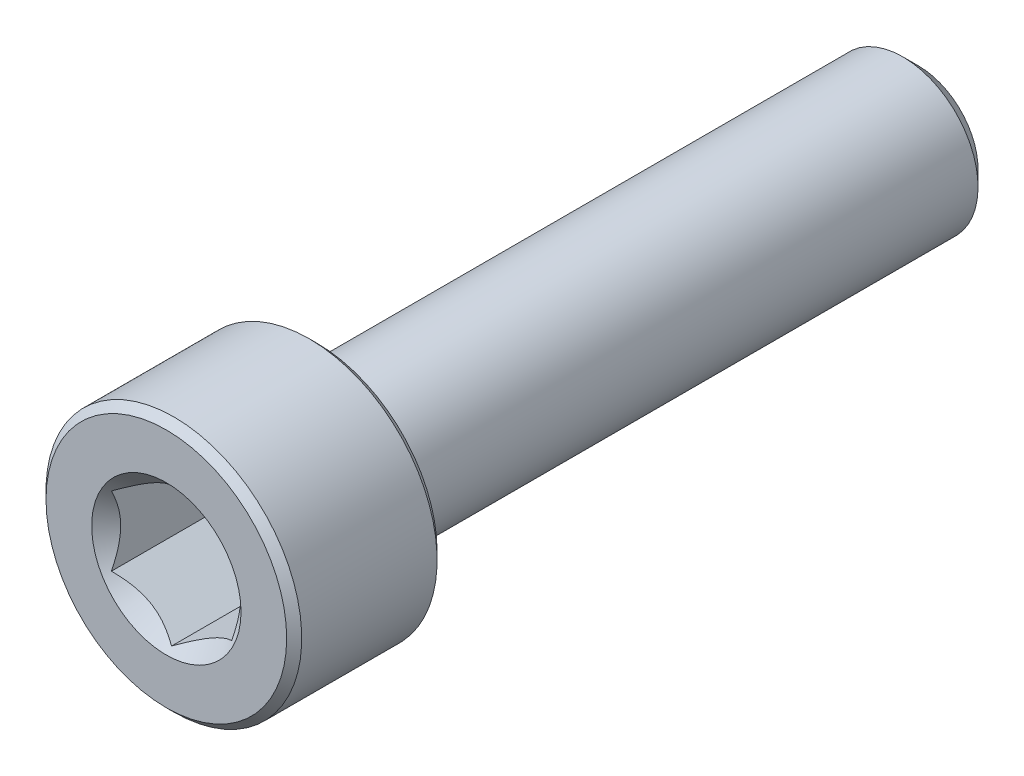
SolidWorks part; units mm, degrees
ref_plane "Front Plane" through (0, 0, 0) normal (0, 0, 1) x (1, 0, 0)
ref_plane "Top Plane" through (0, 0, 0) normal (0, 1, 0) x (1, 0, 0)
ref_plane "Right Plane" through (0, 0, 0) normal (1, 0, 0) x (0, 0, -1)
sketch "Sketch1" plane through (0, 0, 0) normal (1, 0, 0) x (0, 0, -1)
  line L0 (-12.5, 0) -> (12.5, 0) construction
  line L1 (12.5, 0) -> (12.5, 1.9804) construction
  line L2 (12.5, 1.9804) -> (11.9804, 2.5) construction
  line L3 (11.9804, 2.5) -> (11.9, 2.5) construction
  line L4 (11.9, 2.5) -> (-7.5, 2.5) construction
  line L5 (-7.5, 2.5) -> (-7.5, 4.25) construction
  line L6 (-7.5, 4.25) -> (-12.5, 4.25) construction
  line L7 (-12.5, 4.25) -> (-12.5, 0) construction
  line L8 (12.5, 1.9804) -> (12.5, 2.5) construction
  line L9 (12.45, 2.5866) -> (12.85, 1.8938) construction
  line L10 (12.85, 1.8938) -> (13.25, 2.5866) construction
  line L11 (13.25, 2.5866) -> (12.45, 2.5866) construction
  line L12 (12.85, 2.5866) -> (12.85, 2.5) construction
  line L13 (12.85, 1.8938) -> (12.85, 1.9804) construction
  line L14 (12.8, 1.9804) -> (12.9, 1.9804) construction
  line L15 (12.5, 2.5) -> (13.2, 2.5) construction
  line L16 (12.475, 2.5433) -> (13.225, 2.5433) construction
  line L17 (12.5, 0) -> (12.5, -2.5) construction
  line L18 (-7.75, 4.25) -> (-7.5, 4) construction
  line L19 (-12.25, 4.25) -> (-12.5, 4) construction
  line L20 (-7.5, 2.5) -> (-7.5, 0) construction
  line L21 (-7.5, 1.25) -> (-0.8333, 1.25) construction
  line L22 (-0.8333, 1.25) -> (5.8333, 1.25) construction
  line L23 (5.8333, 1.25) -> (12.5, 1.25) construction
  line L24 (-0.8333, 1.25) -> (-0.8333, 2.5) construction
  line L25 (-0.8333, 2.5) -> (-0.8333, 4.25) construction
  line L26 (5.8333, 1.25) -> (5.8333, 4.25) construction
  point P0 (-12.5, 2)
  point P3 (10.5, 2.5)
  point P4 (0, 0)
  point P18 (5.8333, 2.5)
  point P22 (12.85, 1.9804)
  point P24 (11.9, 2.5)
  point P25 (12.85, 2.5)
  point P28 (12.85, 2.5433)
  point P29 (10.5, -2.5)
  point P30 (-0.8333, 2.5)
  point P31 (-10, 4.25)
  point P37 (-8.375, 4.25)
  point P38 (-12.125, 4.25)
  point P45 (-0.8333, 1.25)
  point P46 (5.8333, 1.25)
  dimension "D2" = 0.1
  dimension "D7" = 0.25
  dimension "D8" = 0.25
  dimension "D9" = 0.25
  dimension "D10" = 0.125
  dimension "D11" = 0.625
  dimension "Drive Size" = 4
  dimension "Head Diameter" = 8.5
  dimension "Head Height" = 5
  dimension "Thread Pitch" = 0.8
  dimension "Thread Dia" = 5
  dimension "Length" = 20
  dimension "D12" = 0.6
  dimension "D4" = 2
  dimension "D3" = 45
sketch "Sketch2" plane through (0, 0, 0) normal (1, 0, 0) x (0, 0, -1)
  line L0 (-12.5, 0) -> (-12.5, 4)
  line L1 (-12.25, 4.25) -> (-7.75, 4.25)
  line L2 (-7.5, 4) -> (-7.5, 2.75)
  line L4 (11.9804, 2.5) -> (12.5, 1.9804)
  line L5 (12.5, 1.9804) -> (12.5, 0)
  line L6 (-7.5, 4.25) -> (-12.5, 4.25) construction
  line L7 (12.5, 0) -> (-12.5, 0)
  line L8 (-12.25, 4.25) -> (-12.5, 4) construction
  line L10 (-12.25, 4.25) -> (-12.5, 4)
  line L14 (-7.75, 4.25) -> (-7.5, 4) construction
  line L16 (-7.75, 4.25) -> (-7.5, 4)
  line L17 (-7.5, 2.5) -> (-7.5, 4.25) construction
  line L19 (-7.25, 2.5) -> (11.9804, 2.5)
  line L20 (11.9, 2.5) -> (-7.5, 2.5) construction
  arc A1 (-7.5, 2.75) -> (-7.25, 2.5) centre (-7.25, 2.75) ccw
  dimension "D3" = 0.25
revolve "Revolve1" add sketch "Sketch2" angle 360 about L7
sketch "Sketch3" plane through (0, 0, 12.5) normal (0, 0, 1) x (1, 0, 0)
  line L1 (2, -1.1547) -> (2, 1.1547)
  line L2 (2, 1.1547) -> (0, 2.3094)
  line L3 (0, 2.3094) -> (-2, 1.1547)
  line L4 (-2, 1.1547) -> (-2, -1.1547)
  line L5 (-2, -1.1547) -> (0, -2.3094)
  line L6 (0, -2.3094) -> (2, -1.1547)
  circle A0 centre (0, 0) radius 2 construction
  circle A1 centre (0, 0) radius 4.25 construction
  circle A2 centre (0, 0) radius 4.25 construction
  circle A3 centre (0, 0) radius 2.3094 construction
  point P13 (0, 0)
  dimension "D1" = 4.6188
extrude "Cut-Extrude1" cut sketch "Sketch3" against normal offset from surface (4 mm away) 1 up to face at (0, 4, 7.5)
sketch "Sketch4" plane through (0, 0, 12.5) normal (0, 0, 1) x (1, 0, 0)
  circle A0 centre (0, 0) radius 2.4826
  dimension "D1" = 4.9652
extrude "Cut-Extrude2" cut sketch "Sketch4" against normal up to vertex (2.5 mm away) draft 45 up to point (0, 4.25, 10)
sketch "Sketch11" plane through (0, 0, 0) normal (1, 0, 0) x (0, 0, -1)
  line L0 (-12.5, 0) -> (12.5, 0) construction
  line L1 (-12.5, 0) -> (12.5, 0) construction
  line L2 (-3.75, 0) -> (-3.75, 2.5) construction
  line L3 (11.9, 2.5) -> (-7.5, 2.5) construction
  line L4 (8.75, 0) -> (8.75, 2.5) construction
  line L6 (12.5, 1.9804) -> (12.5, 2.5) construction
  point P2 (-3.75, 0)
  point P3 (8.75, 0)
  dimension "D1" = 3.75
  dimension "D2" = 3.75
sketch "Sketch6" [suppressed] plane through (0, 0, -12.5) normal (0, 0, -1) x (-1, 0, 0)
  circle A0 centre (0, 0) radius 2.5
curve "Helix/Spiral1" [suppressed] pitch 0.8 height 20.8 turns 26
sketch "Sketch10" [suppressed] plane through (0, 0, 0) normal (1, 0, 0) x (0, 0, -1)
  line L0 (-7.25, -4.25) -> (-7.25, 4.25)
  line L5 (-12.5, 0) -> (12.5, 0) construction
  line L6 (-7.25, 2.5) -> (-7.25, -2.5) construction
  point P3 (-7.25, 0)
split "Split1" [suppressed] bodies to split 106
sketch "Sketch7" [suppressed] plane through (0, 0, 0) normal (1, 0, 0) x (0, 0, -1)
  line L0 (12.475, 2.5433) -> (13.225, 2.5433)
  line L1 (13.225, 2.5433) -> (12.9, 1.9804)
  line L2 (12.9, 1.9804) -> (12.8, 1.9804)
  line L3 (12.8, 1.9804) -> (12.475, 2.5433)
sweep "Cut-Sweep1" [suppressed] cut profiles "Sketch7" path "Helix/Spiral1"
sketch "Sketch8" [suppressed] plane through (0, 0, 0) normal (1, 0, 0) x (0, 0, -1)
  line L0 (-7.5, 0) -> (-7.5, 2.5)
  line L1 (-7.25, -2.5) -> (-7.25, 2.5) construction
  line L2 (-7.5, 2.5) -> (-7.25, 2.5)
  line L4 (-7.25, 2.5) -> (-5.8066, 0)
  line L5 (-5.8066, 0) -> (-7.5, 0)
  line L6 (11.9, 2.5) -> (-7.5, 2.5) construction
  line L7 (-12.5, 0) -> (12.5, 0) construction
  dimension "D1" = 60
revolve "Revolve2" [suppressed] add sketch "Sketch8" angle 360 about L5
equation "\"D2@Sketch1\" = \"Thread Pitch@Sketch1\" / 8"
equation "\"D4@Helix/Spiral1\" = \"Thread Pitch@Sketch1\""
equation "\"D7@Sketch1\" = \"Head Height@Sketch1\" * .05"
equation "\"D8@Sketch1\"=\"D7@Sketch1\""
equation "\"D9@Sketch1\"=\"D7@Sketch1\""
equation "\"D10@Sketch1\"=\"D7@Sketch1\"/2"
equation "\"D11@Sketch1\"=\"D10@Sketch1\"*5"
equation "\"D4@Sketch1\"=\"Thread Pitch@Sketch1\"*2.5"
equation "\"D12@Sketch1\"=\"Thread Pitch@Sketch1\"*.75"
equation "\"D3@Helix/Spiral1\"=\"Length@Sketch1\"+\"Thread Pitch@Sketch1\""
equation "\"D3@Sketch2\"=\"Thread Dia@Sketch1\"*0.05"
equation "\"D1@Sketch11\"=\"Length@Sketch1\"*0.1875"
equation "\"D2@Sketch11\"=\"D1@Sketch11\""
equation "\"D1@Sketch4\"=\"D1@Sketch3\"*1.075"
